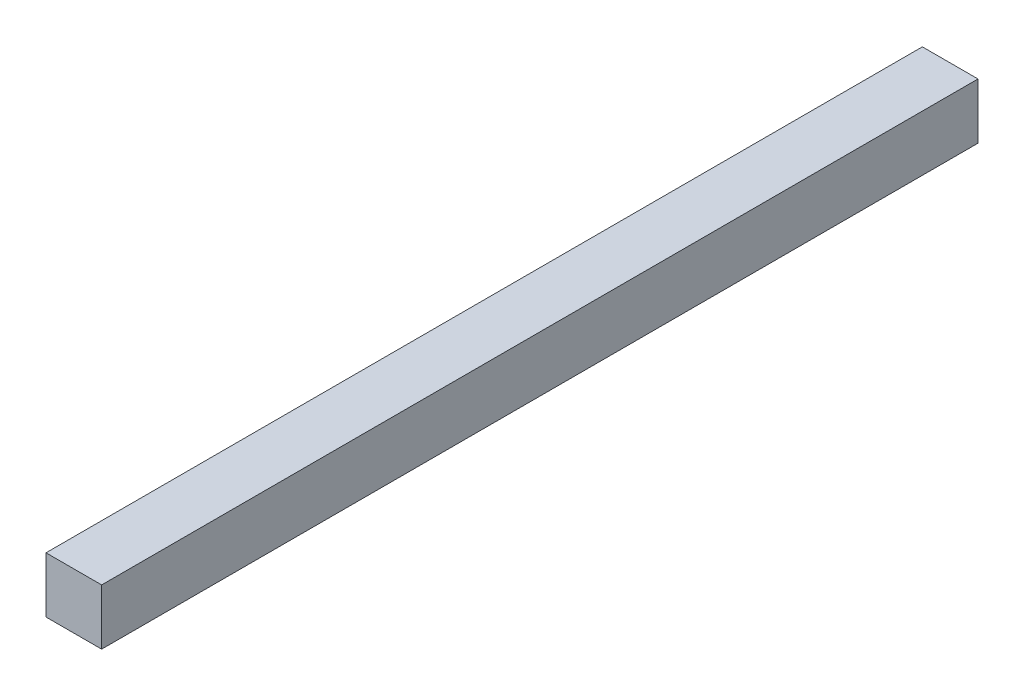
SolidWorks part; units mm, degrees
ref_plane "Front Plane" through (0, 0, 0) normal (0, 0, 1) x (1, 0, 0)
ref_plane "Top Plane" through (0, 0, 0) normal (0, 1, 0) x (1, 0, 0)
ref_plane "Right Plane" through (0, 0, 0) normal (1, 0, 0) x (0, 0, -1)
sketch "Sketch1" plane through (0, 0, 0) normal (0, 0, 1) x (1, 0, 0)
  line L1 (-6.35, -6.35) -> (6.35, -6.35)
  line L2 (-6.35, -6.35) -> (-6.35, 6.35)
  line L3 (-6.35, 6.35) -> (6.35, 6.35)
  line L4 (6.35, -6.35) -> (6.35, 6.35)
  line L5 (-6.35, -6.35) -> (6.35, 6.35) construction
  line L6 (-6.35, 6.35) -> (6.35, -6.35) construction
  point P0 (0, 0)
  point P6 (6.0169, -5)
  dimension "D1" = 12.7
extrude "Boss-Extrude1" add sketch "Sketch1" along normal blind 200
